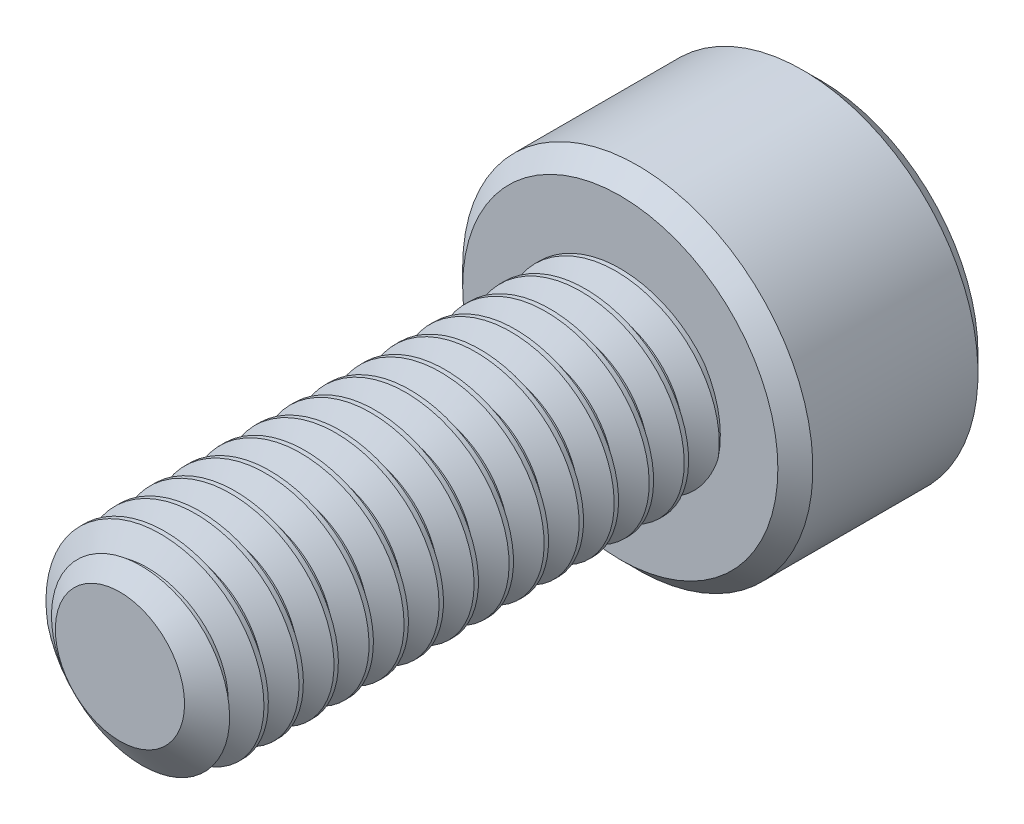
SolidWorks part; units mm, degrees
other "DetailItem1"
ref_plane "Front Plane" through (0, 0, 0) normal (0, 0, 1) x (1, 0, 0)
ref_plane "Top Plane" through (0, 0, 0) normal (0, 1, 0) x (1, 0, 0)
ref_plane "Right Plane" through (0, 0, 0) normal (1, 0, 0) x (0, 0, -1)
sketch "Sketch1" plane through (0, 0, 0) normal (0, 0, 1) x (1, 0, 0)
  circle A0 centre (0, 0) radius 2
  dimension "OD" = 4
extrude "Extrude1" add sketch "Sketch1" against normal blind 10
sketch "Sketch2" plane through (0, 0, 0) normal (0, 0, 1) x (1, 0, 0)
  circle A0 centre (0, 0) radius 2 construction
  circle A1 centre (0, 0) radius 2
curve "Helix/Spiral1" pitch 0.7 height 10.7 radius 2 centre (0, 0, 0) axis (0, 0, -1) start towards (0, 1, 0) parameters "pitch"=0.7
sketch "Sketch3" plane through (0, 0, 0) normal (1, 0, 0) x (0, 0, -1)
  line L0 (-0.6125, 2) -> (-0.35, 1.5453)
  line L1 (-0.35, 1.5453) -> (-0.2625, 1.5453)
  line L2 (-0.2625, 1.5453) -> (0, 2)
  line L3 (-0.6125, 2) -> (0, 2)
  line L4 (-0.3062, 2) -> (-0.3062, 1.5453) construction
  line L5 (-0.4812, 1.7727) -> (-0.1312, 1.7727) construction
  line L6 (0, 2) -> (0, -2) construction
  dimension "D1" = 0.0875
  dimension "D2" = 0.35
  dimension "D3" = 60
sweep "Cut-Sweep1" cut profiles "Sketch3" path "Helix/Spiral1" align with end faces yes
sketch "Sketch4" plane through (0, 0, 0) normal (1, 0, 0) x (0, 0, -1)
  line L0 (0.4962, 2) -> (0, 1.2913)
  line L1 (0, 1.2913) -> (0, 2)
  line L2 (0.4962, 2) -> (0, 2)
  line L3 (-0.6125, 2) -> (0, 2) construction
  line L4 (0, 0) -> (7.0209, 0) construction
  dimension "D1" = 55
  dimension "D2" = 0.254
revolve "Cut-Revolve1" cut sketch "Sketch4" angle 360 about L4
sketch "Sketch6" plane through (0, 0, -10) normal (0, 0, -1) x (-1, 0, 0)
  circle A0 centre (0, 0) radius 3.5
  dimension "head dia" = 7
extrude "Extrude2" add sketch "Sketch6" along normal blind 4
sketch "Sketch7" plane through (0, 0, -14) normal (0, 0, -1) x (-1, 0, 0)
  line L1 (0, 1.7321) -> (-1.5, 0.866)
  line L2 (-1.5, 0.866) -> (-1.5, -0.866)
  line L3 (-1.5, -0.866) -> (0, -1.7321)
  line L4 (0, -1.7321) -> (1.5, -0.866)
  line L5 (1.5, -0.866) -> (1.5, 0.866)
  line L6 (1.5, 0.866) -> (0, 1.7321)
  circle A0 centre (0, 0) radius 1.5 construction
  dimension "hex dia" = 3
extrude "Cut-Extrude1" cut sketch "Sketch7" against normal blind 2.25
sketch "Sketch8" plane through (0, 0, -14) normal (0, 0, -1) x (-1, 0, 0)
  circle A0 centre (0, 0) radius 1.7321
extrude "Cut-Extrude2" cut sketch "Sketch8" against normal through all draft 45
chamfer "Chamfer1" distance 0.35 angle 45 2 edges at (-3.5, 0, -14) (-3.5, 0, -10)
sketch "Sketch10" plane through (0, 0, -10) normal (0, 0, 1) x (1, 0, 0)
  circle A1 centre (0, 0) radius 2
  circle A2 centre (0, 0) radius 2
  dimension "D1" = 0
ref_plane "Plane1" through (0, 0, 0) normal (0, 0, 1) x (1, 0, 0)
extrude "partial thread" [suppressed] add sketch "Sketch10" along normal up to surface (10 mm away) separate body up to plane "Plane1"
chamfer "Chamfer2" [suppressed] distance 0.08 angle 45
combine bodies "Combine1" [suppressed] operation type add bodies to combine 107 108
sketch "Sketch9" plane through (0, 0, 0) normal (1, 0, 0) x (0, 0, -1)
  line L0 (0, 2) -> (0, -2) construction
  line L1 (1.75, 2) -> (1.75, -2) construction
  dimension "D1" = 1.75
equation "\"D3@Helix/Spiral1\" = \"screw length@Extrude1\"+\"pitch@Helix/Spiral1\""
equation "\"D1@Sketch3\" = \"pitch@Helix/Spiral1\"*.125"
equation "\"D2@Sketch3\" = \"pitch@Helix/Spiral1\"*.5"
equation "\"D1@Cut-Extrude1\" = \"hex dia@Sketch7\"*.75"
equation "\"D1@Chamfer1\" = \"head dia@Sketch6\"*.05"
equation "\"D1@Sketch9\" = \"pitch@Helix/Spiral1\"*2.5"
equation "\"D1@Chamfer2\"=\"OD@Sketch1\"*.02"
